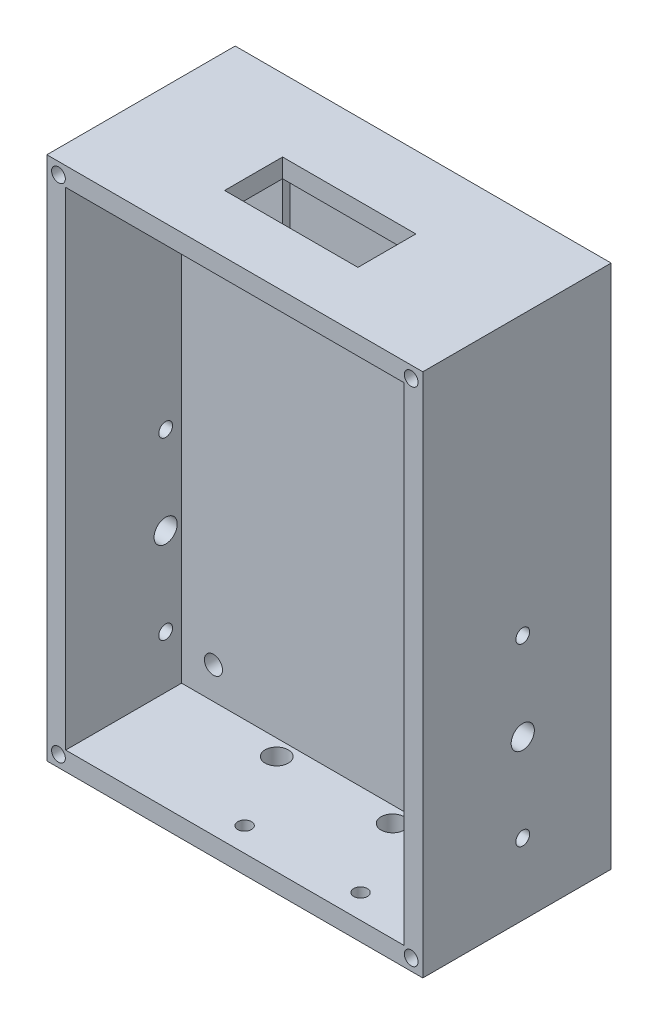
SolidWorks part; units mm, degrees
material "6061 合金"
ref_plane "前视基准面" through (0, 0, 0) normal (0, 0, 1) x (1, 0, 0)
ref_plane "上视基准面" through (0, 0, 0) normal (0, 1, 0) x (1, 0, 0)
ref_plane "右视基准面" through (0, 0, 0) normal (1, 0, 0) x (0, 0, -1)
other "Configuration Table"
sketch "草图1" plane through (0, 0, 0) normal (0, 0, 1) x (1, 0, 0)
  line L0 (-0.5, -0.5) -> (-0.5, 33.14)
  line L1 (0, 0) -> (22.35, 0)
  line L2 (0, 0) -> (0, 32.64)
  line L3 (0, 32.64) -> (22.35, 32.64)
  line L4 (22.35, 0) -> (22.35, 32.64)
  line L5 (-0.5, 33.14) -> (22.85, 33.14)
  line L6 (22.85, -0.5) -> (22.85, 33.14)
  line L7 (-0.5, -0.5) -> (22.85, -0.5)
  line L12 (24.15, -1.8) -> (24.15, 34.44)
  line L13 (-1.8, 34.44) -> (24.15, 34.44)
  line L14 (-1.8, -1.8) -> (-1.8, 34.44)
  line L15 (-1.8, -1.8) -> (24.15, -1.8)
  dimension "D1" = 22.35
  dimension "D2" = 32.64
  dimension "D4" = 1.8
  dimension "D3" = 0.5
extrude "凸台-拉伸4" add sketch "草图1" along normal blind 5 contours L13 L14 L15 L12
extrude "凸台-拉伸6" add sketch "草图1<4>" along normal blind 13 contours L13 L14 L15 L12 | L5 L6 L7 L0
sketch "草图1<4>" plane through (0, 0, 0) normal (0, 0, 1) x (1, 0, 0) same geometry as "草图1"
sketch "草图2" plane through (0, 34.44, 0) normal (0, 1, 0) x (1, 0, 0)
  line L1 (6.47, -5) -> (15.67, -5)
  line L2 (6.47, -5) -> (6.47, -9)
  line L3 (6.47, -9) -> (15.67, -9)
  line L4 (15.67, -5) -> (15.67, -9)
extrude "切除-拉伸1" cut sketch "草图2" against normal blind 2 contours L2 L1 L4 L3
hole_wizard "M1.6 螺纹孔1" positions "草图3" profile "草图4" tap size "M1.6" standard "GB" end condition through all
sketch "草图3" plane through (0, 0, 5) normal (0, 0, 1) x (1, 0, 0)
  point P0 (1.7, 1.7)
  point P2 (20.65, 1.7)
  point P4 (20.65, 30.94)
  point P6 (1.7, 30.94)
sketch "草图4" plane through (1.7, 1.7, 5) normal (1, 0, 0) x (0, -1, 0)
  line L0 (0, 0) -> (0, 5)
  line L1 (0, 5) -> (0.625, 5)
  line L2 (0.625, 5) -> (0.625, 0)
  line L5 (0.625, 0) -> (0, 0)
  line L11 (0, -6.35) -> (0, 107.95) construction
  dimension "通孔螺纹孔钻头直径" = 1.25
  dimension "通孔螺纹孔钻头深度" = 5
cosmetic thread "孔螺纹线1" parameters "D2"=1.6
cosmetic thread "孔螺纹线2" parameters "D2"=1.6
cosmetic thread "孔螺纹线3" parameters "D2"=1.6
cosmetic thread "孔螺纹线4" parameters "D2"=1.6
sketch "草图5" plane through (0, 0, 5) normal (0, 0, 1) x (1, 0, 0)
  line L1 (6.47, 33.14) -> (15.67, 33.14)
  line L2 (6.47, 33.14) -> (6.47, 27.14)
  line L3 (6.47, 27.14) -> (15.67, 27.14)
  line L4 (15.67, 33.14) -> (15.67, 27.14)
extrude "切除-拉伸2" cut sketch "草图5" against normal blind 0.5 contours L2 L1 L4 L3
sketch "草图6" plane through (24.15, 0, 0) normal (1, 0, 0) x (0, 0, -1)
  circle A0 centre (-6.1, 9.168) radius 0.8
extrude "切除-拉伸3" cut sketch "草图6" against normal through all
hole_wizard "M1.2x0.25 螺纹孔1" positions "3D草图1" profile "草图8" tap size "M1.2x0.25" standard "GB" end condition through all
sketch3d "3D草图1"
  point P0 (24.15, 15.218, 6.1)
  point P2 (24.15, 3.118, 6.1)
sketch "草图8" plane through (24.15, 15.218, 6.1) normal (0, 1, 0) x (0, 0, -1)
  line L0 (0, 0) -> (0, 25.95)
  line L1 (0, 25.95) -> (0.475, 25.95)
  line L2 (0.475, 25.95) -> (0.475, 0)
  line L5 (0.475, 0) -> (0, 0)
  line L11 (0, -6.35) -> (0, 107.95) construction
  dimension "通孔螺纹孔钻头直径" = 0.95
  dimension "通孔螺纹孔钻头深度" = 25.95
cosmetic thread "孔螺纹线5" parameters "D2"=1.2
cosmetic thread "孔螺纹线6" parameters "D2"=1.2
sketch "草图9" plane through (0, -1.8, 0) normal (0, -1, 0) x (1, 0, 0)
  circle A0 centre (7.166, 6.1) radius 0.8
  circle A1 centre (15.166, 6.1) radius 0.8
extrude "切除-拉伸4" cut sketch "草图9" against normal blind 2
hole_wizard "M1.2x0.25 螺纹孔2" positions "3D草图3" profile "草图11" tap size "M1.2x0.25" standard "GB"
sketch3d "3D草图3"
  line L11 (4.141, -1.8, 0.8605) -> (7.8363, -1.8, 0.8605)
  line L14 (15.166, -0.5, 6.1) -> (15.166, -1.8, 6.1) construction
  line L23 (15.166, -1.8, 6.1) -> (15.166, -1.8, 11.4857)
  circle A0 centre (7.166, -1.8, 6.1) radius 0.8 construction
  circle A1 centre (15.166, -1.8, 6.1) radius 0.8 construction
  point P0 (4.141, -1.8, 0.8605)
  point P2 (10.191, -1.8, 11.3395)
  point P4 (12.141, -1.8, 0.8605)
  point P6 (18.191, -1.8, 11.3395)
  point P12 (7.166, -2.6, 6.1)
  point P18 (15.166, -2.6, 6.1)
  dimension "D2" = 6.05
  dimension "D1" = 6.05
  dimension "D3" = 6.05
  dimension "D4" = 6.05
sketch "草图11" plane through (4.141, -1.8, 0.8605) normal (1, 0, 0) x (0, 0, -1)
  line L0 (0, 0) -> (0, 3.4354)
  line L1 (0, 3.4354) -> (0.475, 3.15)
  line L2 (0.475, 3.15) -> (0.475, 0)
  line L5 (0.475, 0) -> (0, 0)
  line L10 (0, 3.4354) -> (-0.475, 3.15) construction
  line L11 (0, -6.35) -> (0, 107.95) construction
  dimension "螺纹孔钻头直径" = 0.95
  dimension "螺纹孔钻头深度" = 3.15
  dimension "导头角度" = 118
cosmetic thread "孔螺纹线7" parameters "D1"=2.4, "D2"=1.2
cosmetic thread "孔螺纹线8" parameters "D1"=2.4, "D2"=1.2
cosmetic thread "孔螺纹线9" parameters "D1"=2.4, "D2"=1.2
cosmetic thread "孔螺纹线10" parameters "D1"=2.4, "D2"=1.2
hole_wizard "M1.2x0.25 螺纹孔3" positions "3D草图4" profile "草图12" tap size "M1.2x0.25" standard "GB"
sketch3d "3D草图4"
  point P0 (-1, 33.64, 13)
  point P2 (23.35, 33.64, 13)
  point P4 (-1, -1, 13)
  point P6 (23.35, -1, 13)
  point P17 (0, 0, 0)
  point P18 (0, 0, 0)
  point P19 (0, 0, 0)
  point P20 (0, 0, 0)
sketch "草图12" plane through (-1, 33.64, 13) normal (1, 0, 0) x (0, -1, 0)
  line L0 (0, 0) -> (0, 3.4354)
  line L1 (0, 3.4354) -> (0.475, 3.15)
  line L2 (0.475, 3.15) -> (0.475, 0)
  line L5 (0.475, 0) -> (0, 0)
  line L10 (0, 3.4354) -> (-0.475, 3.15) construction
  line L11 (0, -6.35) -> (0, 107.95) construction
  dimension "螺纹孔钻头直径" = 0.95
  dimension "螺纹孔钻头深度" = 3.15
  dimension "导头角度" = 118
cosmetic thread "孔螺纹线11" parameters "D1"=2.4, "D2"=1.2
cosmetic thread "孔螺纹线12" parameters "D1"=2.4, "D2"=1.2
cosmetic thread "孔螺纹线13" parameters "D1"=2.4, "D2"=1.2
cosmetic thread "孔螺纹线14" parameters "D1"=2.4, "D2"=1.2
